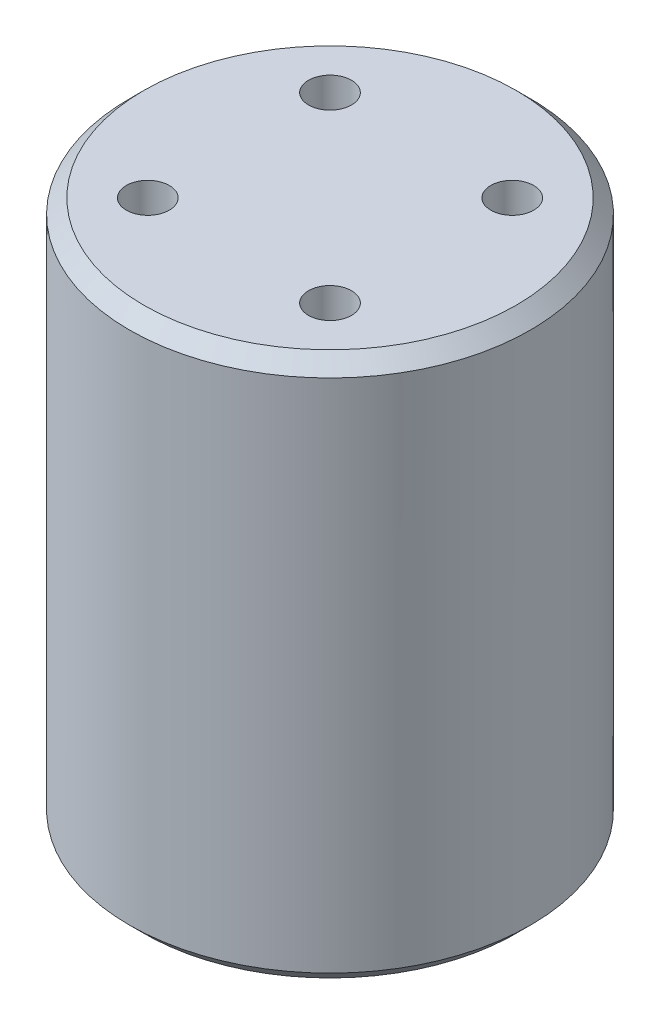
SolidWorks part; units mm, degrees
ref_plane "Front Plane" through (0, 0, 0) normal (0, 0, 1) x (1, 0, 0)
ref_plane "Top Plane" through (0, 0, 0) normal (0, 1, 0) x (1, 0, 0)
ref_plane "Right Plane" through (0, 0, 0) normal (1, 0, 0) x (0, 0, -1)
sketch "Sketch1" plane through (0, 0, 0) normal (0, 1, 0) x (1, 0, 0)
  circle A0 centre (0, 0) radius 14
  dimension "D1" = 28
extrude "Boss-Extrude1" add sketch "Sketch1" along normal blind 28 and the other way blind 10
sketch "Sketch2" plane through (0, 28, 0) normal (0, 1, 0) x (1, 0, 0)
  line L0 (0, 0) -> (0, 18.7078) construction
  line L1 (-6.364, 6.364) -> (0, 0) construction
  line L2 (0, 0) -> (-6.364, 6.364) construction
  circle A0 centre (0, 0) radius 9 construction
  circle A1 centre (-6.364, 6.364) radius 1.5
  circle A2 centre (6.364, 6.364) radius 1.5
  circle A3 centre (6.364, -6.364) radius 1.5
  circle A4 centre (-6.364, -6.364) radius 1.5
  dimension "D1" = 18
  dimension "D2" = 3
  dimension "D3" = 45
  dimension "D5" = 9
  dimension "D4" = 4
extrude "Cut-Extrude1" cut sketch "Sketch2" against normal blind 8
sketch "Sketch3" plane through (0, -10, 0) normal (0, -1, 0) x (1, 0, 0)
  line L0 (0, 0) -> (0, 14) construction
  line L1 (-6.364, 6.364) -> (0, 0) construction
  line L2 (0, 0) -> (-6.364, 6.364) construction
  line L4 (-20.5662, 5) -> (-8.4338, 5)
  line L5 (-20.5662, 5) -> (-20.5662, -5)
  line L6 (-20.5662, -5) -> (-8.4338, -5)
  line L7 (-7.4338, 4) -> (-7.4338, -4)
  line L8 (-20.5662, 5) -> (-7.4338, -5) construction
  line L9 (-20.5662, -5) -> (-7.4338, 5) construction
  circle A0 centre (0, 0) radius 9 construction
  circle A1 centre (0, 0) radius 14 construction
  circle A2 centre (-6.364, 6.364) radius 1.5
  circle A3 centre (6.364, 6.364) radius 1.5
  circle A4 centre (6.364, -6.364) radius 1.5
  circle A5 centre (-6.364, -6.364) radius 1.5
  arc A6 (-8.4338, -5) -> (-7.4338, -4) centre (-8.4338, -4) ccw
  arc A7 (-8.4338, 5) -> (-7.4338, 4) centre (-8.4338, 4) cw
  circle A8 centre (0, 0) radius 2
  point P9 (-14, 0)
  circle M14 centre (0, 0) radius 14
  dimension "D1" = 18
  dimension "D2" = 3
  dimension "D7" = 1
  dimension "D8" = 4
  dimension "D3" = 45
  dimension "D5" = 9
  dimension "D6" = 10
  dimension "D4" = 4
extrude "Cut-Extrude2" cut sketch "Sketch3" against normal blind 4 contours A2 | A3 | A5 | A4 region at (-6.364, -10, 6.364) region at (6.364, -10, 6.364) region at (6.364, -10, -6.364) region at (-6.364, -10, -6.364)
extrude "Cut-Extrude3" cut sketch "Sketch3<3>" against normal blind 5 contours A7 L4 L6 A6 L7 M14 | L5 L6 L4 M14 region at (-17.1259, -10, 0) region at (-10.5912, -10, 0)
sketch "Sketch3<3>" plane through (0, -10, 0) normal (0, -1, 0) x (1, 0, 0) same geometry as "Sketch3"
extrude "Boss-Extrude2" add sketch "Sketch3<4>" along normal blind 1 contours A8 region at (0, -10, 0)
sketch "Sketch3<4>" plane through (0, -10, 0) normal (0, -1, 0) x (1, 0, 0) same geometry as "Sketch3"
chamfer "Chamfer1" distance 1 angle 45 2 edges at (0, 28, 14) (14, -10, 0)
